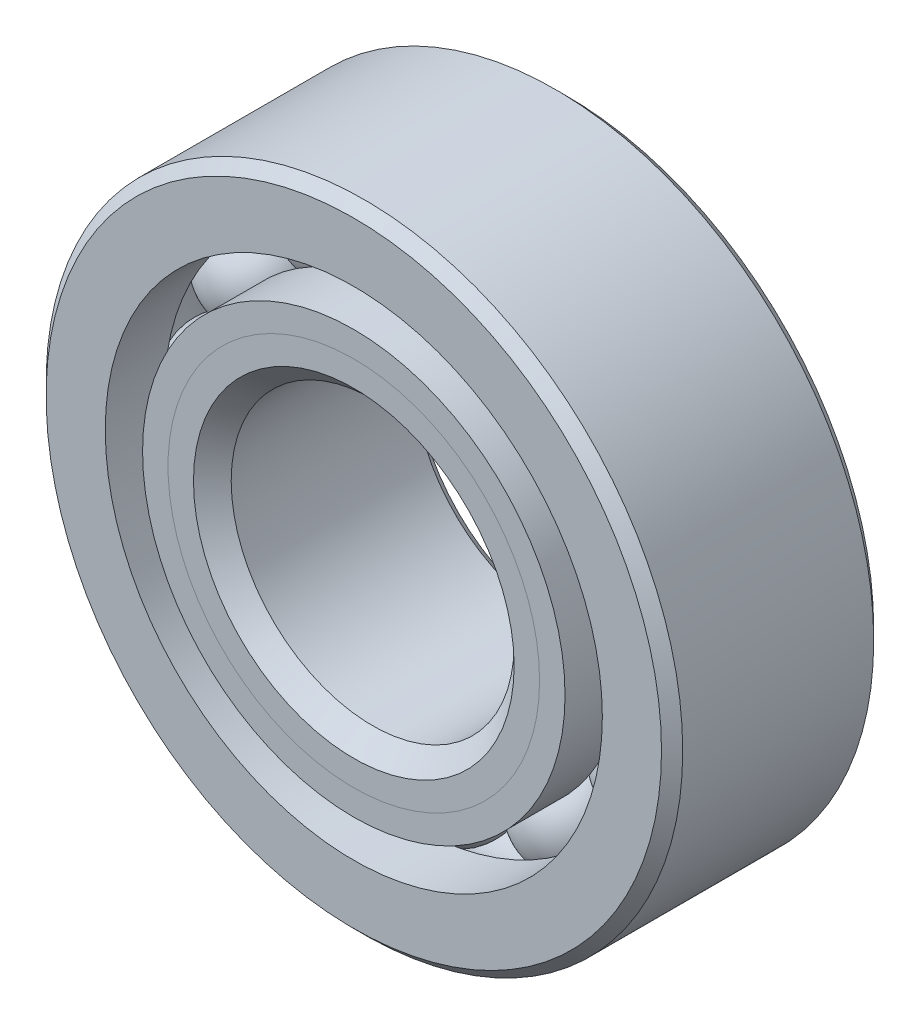
SolidWorks part; units mm, degrees
material "1060 Alloy"
ref_plane "Front Plane" through (0, 0, 0) normal (0, 0, 1) x (1, 0, 0)
ref_plane "Top Plane" through (0, 0, 0) normal (0, 1, 0) x (1, 0, 0)
ref_plane "Right Plane" through (0, 0, 0) normal (1, 0, 0) x (0, 0, -1)
sketch "Sketch1" plane through (0, 0, 0) normal (1, 0, 0) x (0, 0, -1)
  line L0 (-4.7625, 0) -> (4.7625, 0) construction
  line L1 (0, 14.2875) -> (0, -14.2875) construction
  line L2 (4.2863, 14.2875) -> (-4.2863, 14.2875)
  line L3 (-4.2863, 14.2875) -> (-4.7625, 13.8112)
  line L4 (-4.7625, 13.8112) -> (-4.7625, 11.1561)
  line L5 (-4.7625, 11.1561) -> (-2.1167, 11.1561)
  line L6 (4.7625, 11.1561) -> (2.1167, 11.1561)
  line L7 (4.7625, 13.8112) -> (4.7625, 11.1561)
  line L8 (4.2863, 14.2875) -> (4.7625, 13.8112)
  line L9 (0, 14.2875) -> (0, 10.3187) construction
  line L10 (0, 10.3187) -> (0, 6.35) construction
  arc A0 (-2.1167, 11.1561) -> (2.1167, 11.1561) centre (0, 10.3187) cw
  point P14 (0, 6.35)
  dimension "D3" = 4.2333
  dimension "D1" = 45
  dimension "Width" = 9.525
  dimension "OD" = 28.575
  dimension "D2" = 0.4763
  dimension "Shaft Dia" = 12.7
  dimension "D4" = 0.8374
revolve "Revolve1" add sketch "Sketch1" angle 360 about L0
sketch "Sketch2" plane through (0, 0, 0) normal (1, 0, 0) x (0, 0, -1)
  line L0 (-4.7625, 9.4814) -> (-2.1167, 9.4814)
  line L1 (-4.7625, 13.8112) -> (-4.7625, -13.8112) construction
  line L2 (-4.7625, 9.4814) -> (-4.7625, 8.3388)
  line L3 (-4.7625, 8.3388) -> (-3.6199, 7.1962)
  line L4 (-3.6199, 7.1962) -> (0, 7.1962)
  line L5 (0, 14.2875) -> (0, -14.2875) construction
  line L6 (0, 7.1962) -> (0, 8.0425)
  line L7 (0, 8.0425) -> (0, 6.35) construction
  line L8 (-4.7625, 9.4814) -> (-4.7625, 7.1962) construction
  line L9 (-4.7625, 7.1962) -> (-3.6199, 7.1962) construction
  arc A0 (-2.1167, 9.4814) -> (0, 8.0425) centre (0, 10.3187) ccw
  arc A1 (2.1167, 11.1561) -> (-2.1167, 11.1561) centre (0, 10.3187) ccw construction
  circle A2 centre (0, 10.3187) radius 2.2763 construction
  dimension "D1" = 45
revolve "Revolve2" add sketch "Sketch2" angle 360 about L0
sketch "Sketch3" plane through (0, 0, 0) normal (1, 0, 0) x (0, 0, -1)
  line L0 (-4.7625, 8.3388) -> (-3.6199, 7.1962)
  line L1 (-3.6199, 7.1962) -> (0, 7.1962)
  line L2 (0, 7.1962) -> (0, 8.0425)
  line L3 (-4.7625, 8.3388) -> (-4.7625, 7.1962)
  line L4 (-4.7625, 9.4814) -> (-4.7625, 7.1962) construction
  line L5 (-4.7625, 7.1962) -> (-3.9163, 6.35)
  line L6 (-3.9163, 6.35) -> (4.2863, 6.35)
  line L7 (4.2863, 14.2875) -> (4.2863, -14.2875) construction
  line L8 (4.2863, 6.35) -> (4.7625, 6.8263)
  line L9 (4.7625, -13.8112) -> (4.7625, 13.8112) construction
  line L10 (4.7625, 6.8263) -> (4.7625, 9.4814)
  line L11 (4.7625, 9.4814) -> (2.1167, 9.4814)
  line L13 (4.2863, 14.2875) -> (4.7625, 13.8112) construction
  circle A0 centre (0, 10.3187) radius 2.2763 construction
  arc A1 (2.1167, 9.4814) -> (0, 8.0425) centre (0, 10.3187) cw
revolve "Revolve3" add sketch "Sketch3" angle 360 about L0
sketch "Sketch4" plane through (0, 0, 0) normal (1, 0, 0) x (0, 0, -1)
  line L0 (-2.2763, 10.3187) -> (2.2763, 10.3187)
  circle A1 centre (0, 10.3187) radius 2.2763 construction
  arc A2 (-2.2763, 10.3187) -> (2.2763, 10.3187) centre (0, 10.3187) cw
  arc A3 (2.1167, 11.1561) -> (-2.1167, 11.1561) centre (0, 10.3187) ccw construction
revolve "Revolve4" add sketch "Sketch4" angle 360 about L0
ref_axis "Axis1" through (0, 0, -4.7625) along (0, 0, 1)
pattern_circular "CirPattern1" count 12 every 30 about axis through (0, 0, -4.7625) along (0, 0, 1) of bodies 104
equation "\"D2@Sketch1\" = \"Width@Sketch1\"*.05"
equation "\"D3@Sketch1\" = \"Width@Sketch1\"/2.25"
equation "\"D4@Sketch1\" = (((\"OD@Sketch1\"-\"Width@Sketch1\")/2)/3.25)/3.5"
equation "\"D2@CirPattern1\" = 360/\"Balls@CirPattern1\""
